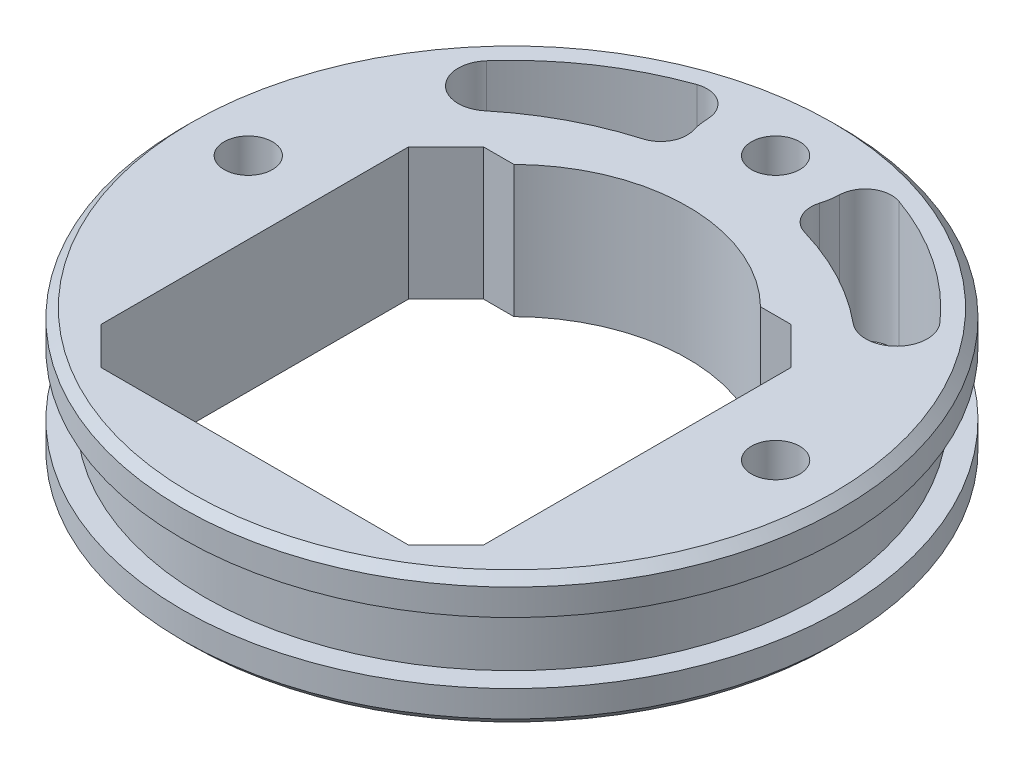
SolidWorks part; units mm, degrees
ref_plane "Front Plane" through (0, 0, 0) normal (0, 0, 1) x (1, 0, 0)
ref_plane "Top Plane" through (0, 0, 0) normal (0, 1, 0) x (1, 0, 0)
ref_plane "Right Plane" through (0, 0, 0) normal (1, 0, 0) x (0, 0, -1)
sketch "Sketch1" plane through (0, 0, 0) normal (0, 1, 0) x (1, 0, 0)
  line L0 (0, 0) -> (0, -7.5) construction
  line L1 (-17.4944, 14.25) -> (-14.0334, 14.25)
  line L2 (17.4944, 14.25) -> (21.75, 9.9944)
  line L3 (21.75, 9.9944) -> (21.75, -24.9944)
  line L4 (21.75, -24.9944) -> (17.4944, -29.25)
  line L5 (17.4944, -29.25) -> (-17.4944, -29.25)
  line L6 (-17.4944, -29.25) -> (-21.75, -24.9944)
  line L7 (-21.75, -24.9944) -> (-21.75, 9.9944)
  line L8 (-21.75, 9.9944) -> (-17.4944, 14.25)
  line L9 (14.0334, 14.25) -> (17.4944, 14.25)
  circle A0 centre (0, 0) radius 35 construction
  circle A1 centre (0, -7.5) radius 27.9127 construction
  circle A2 centre (0, 0) radius 30 construction
  circle A3 centre (0, 30) radius 2.75
  circle A4 centre (30, 0) radius 2.75
  circle A5 centre (-30, 0) radius 2.75
  circle A6 centre (0, 0) radius 37.5
  arc A7 (-20.9585, 17.8769) -> (20.9585, 17.8769) centre (0, -7.5) ccw construction
  arc A8 (7.1823, 27.8402) -> (7.4969, 29.7857) centre (0, 30) ccw
  arc A9 (6.4062, 33.9) -> (-6.4062, 33.9) centre (0, 0) ccw construction
  arc A10 (-25.8051, 22.8986) -> (-20.9585, 17.8769) centre (-23.1872, 20.5755) ccw
  arc A11 (20.9585, 17.8769) -> (25.8051, 22.8986) centre (23.1872, 20.5755) ccw
  arc A12 (-5.5389, 24.9433) -> (5.5389, 24.9433) centre (0, 30) ccw construction
  arc A13 (5.5389, 24.9433) -> (-5.5389, 24.9433) centre (0, -7.5) ccw construction
  arc A14 (-9.2152, 24.0963) -> (-20.9585, 17.8769) centre (0, -7.5) ccw
  arc A15 (20.9585, 17.8769) -> (9.2152, 24.0963) centre (0, -7.5) ccw
  arc A16 (25.8051, 22.8986) -> (11.4953, 32.5286) centre (0, 0) ccw
  arc A17 (-11.4953, 32.5286) -> (-25.8051, 22.8986) centre (0, 0) ccw
  arc A18 (-25.8051, 22.8986) -> (25.8051, 22.8986) centre (0, 0) ccw construction
  arc A19 (-7.4969, 29.7857) -> (-7.1823, 27.8402) centre (0, 30) ccw
  arc A20 (6.4062, 33.9) -> (-6.4062, 33.9) centre (0, 30) ccw construction
  arc A21 (11.4953, 32.5286) -> (7.4969, 29.7857) centre (10.4957, 29.7) ccw
  arc A22 (7.1823, 27.8402) -> (9.2152, 24.0963) centre (10.0552, 26.9763) ccw
  arc A23 (-9.2152, 24.0963) -> (-7.1823, 27.8402) centre (-10.0552, 26.9763) ccw
  arc A24 (-11.4953, 32.5286) -> (-7.4969, 29.7857) centre (-10.4957, 29.7) cw
  arc A25 (14.0334, 14.25) -> (-14.0334, 14.25) centre (0, 0) ccw
  dimension "D1" = 43.5
  dimension "D2" = 70
  dimension "D5" = 60
  dimension "D6" = 5.5
  dimension "D7" = 2.5
  dimension "D8" = 3
  dimension "D9" = 5
  dimension "D10" = 3.5
  dimension "D11" = 3
  dimension "D12" = 20
  dimension "D3" = 7.5
  dimension "D4" = 55.5
extrude "Boss-Extrude1" add sketch "Sketch1" along normal mid plane 15
sketch "Sketch2" plane through (0, 0, 0) normal (0, 1, 0) x (1, 0, 0)
  circle A0 centre (0, 0) radius 35
  dimension "D1" = 70
extrude "Cut-Extrude-Thin1" cut sketch "Sketch2" against normal mid plane 7 thin thin type one direction wall 10
chamfer "Chamfer1" distance 1 angle 45 2 edges at (0, -7.5, 37.5) (0, 7.5, 37.5)
